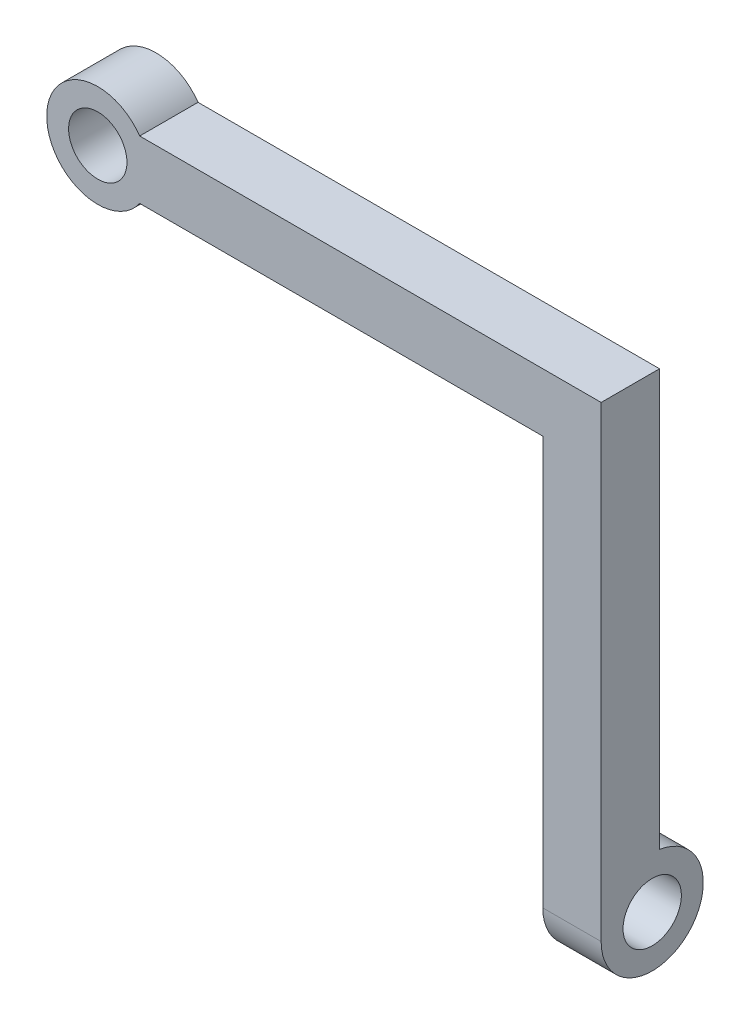
SolidWorks part; units mm, degrees
ref_plane "Plano frontal" through (0, 0, 0) normal (0, 0, 1) x (1, 0, 0)
ref_plane "Plano superior" through (0, 0, 0) normal (0, 1, 0) x (1, 0, 0)
ref_plane "Plano direito" through (0, 0, 0) normal (1, 0, 0) x (0, 0, -1)
sketch "Esboço1" plane through (0, 0, 0) normal (0, 0, 1) x (1, 0, 0)
  line L0 (5.7446, 64) -> (69, 64)
  line L2 (61, 7) -> (61, -7)
  line L3 (61, -7) -> (69, -7)
  line L4 (69, 32) -> (69, -7)
  line L5 (61, 7) -> (69, -7) construction
  line L6 (61, -7) -> (69, 32) construction
  line L7 (69, 64) -> (69, 32)
  line L8 (5.7446, 56) -> (61, 56)
  line L9 (61, 56) -> (61, 7)
  line L10 (61, 64) -> (61, 56) construction
  line L11 (69, 56) -> (61, 56) construction
  circle A3 centre (0, 60) radius 4
  arc A4 (5.7446, 64) -> (5.7446, 56) centre (0, 60) ccw
  point P3 (36, 7.3085)
  point P7 (44, 7)
  point P9 (0, 0)
  point P15 (36.1869, 7)
  point P16 (36.3859, 37.001)
  point P17 (65, 0)
  point P18 (0, 0)
  point P19 (29.9558, -7)
  point P21 (36.7734, 31.5)
  point P22 (29.4412, 7)
  point P23 (44, 7)
  dimension "D1" = 8
  dimension "D4" = 14
  dimension "D5" = 8
  dimension "D2" = 60
  dimension "D3" = 14
  dimension "D6" = 65
extrude "Ressalto-extrusão1" add sketch "Esboço1" along normal blind 14
sketch "Esboço2" plane through (69, 0, 0) normal (1, 0, 0) x (0, 0, -1)
  line L2 (-6, 67) -> (-6, 6.9282)
  line L3 (0, 67) -> (-14, 67) construction
  line L4 (-6, 67) -> (0, 67)
  line L5 (0, 53) -> (0, 67) construction
  line L6 (0, 67) -> (0, 0)
  line L8 (-14, -7) -> (0, -7) construction
  circle A0 centre (-7, 0) radius 7
  circle A1 centre (-7, 0) radius 4
  point P4 (-7.2675, 0)
  point P5 (0, 0)
  point P6 (-4.834, 0)
  point P9 (-7, -7)
  line M1 (0, -7) -> (0, 64)
  line M3 (-14, 64) -> (-14, -7)
  line M4 (-14, -7) -> (0, -7)
  dimension "D1" = 14
  dimension "D2" = 8
  dimension "D3" = 6
extrude "Corte-extrusão1" cut sketch "Esboço2" against normal through all contours A0 M4 M1 | A0 M3 M4 | A1 | L6 L4 L2 | A0 L2 M1 region at (69, 36.1061, 2.959) region at (69, -5.4364, 1.5636) region at (69, -5.4364, 12.4364) region at (69, 0, 7)
